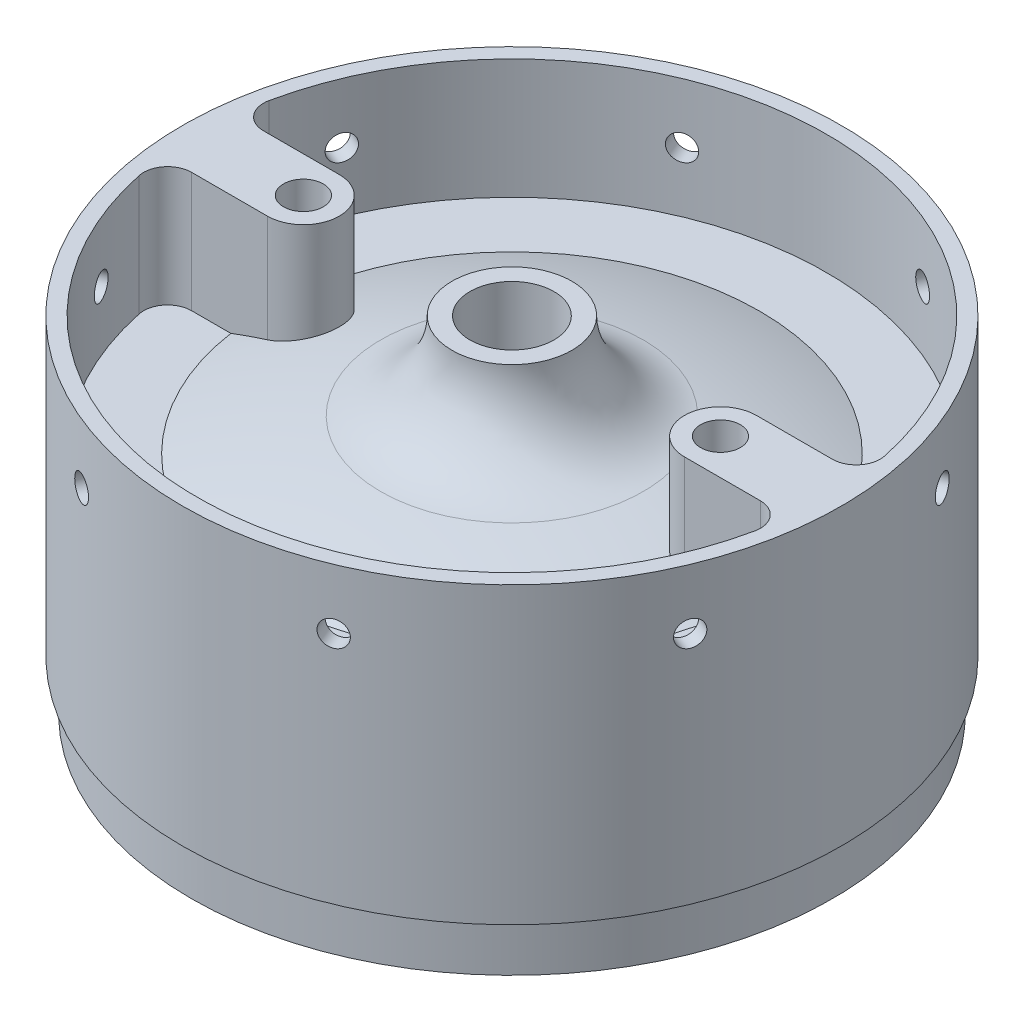
SolidWorks part; units mm, degrees
material "6061-T6 (SS)"
ref_plane "Front Plane" through (0, 0, 0) normal (0, 0, 1) x (1, 0, 0)
ref_plane "Top Plane" through (0, 0, 0) normal (0, 1, 0) x (1, 0, 0)
ref_plane "Right Plane" through (0, 0, 0) normal (1, 0, 0) x (0, 0, -1)
ref_axis "Axis1" through (0, 127.061, 0) along (0, -1, 0)
sketch "Sketch1" plane through (0, 0, 0) normal (0, 0, 1) x (1, 0, 0)
  line L0 (-69.85, 10.6249) -> (-69.85, 73.025)
  line L1 (-67.945, 9.525) -> (-69.85, 10.6249)
  line L2 (0, 127.061) -> (0, -81.9141) construction
  line L3 (-8.9065, 73.025) -> (-12.7, 73.025)
  line L4 (-67.945, 9.525) -> (-67.945, 0)
  line L5 (-67.945, 0) -> (-66.675, 0)
  line L6 (55, 0) -> (-55, 0) construction
  line L7 (-66.675, 73.025) -> (-69.85, 73.025)
  line L8 (-69.85, 10.6249) -> (-67.945, 9.525)
  line L9 (-66.675, 47.625) -> (-52.5032, 47.625)
  line L10 (-8.9065, 73.025) -> (-8.9065, 57.785)
  line L11 (-66.675, 47.625) -> (-66.675, 73.025)
  line L15 (-66.675, 0) -> (-66.675, 9.525)
  line L16 (-66.675, 9.525) -> (-64.3936, 22.4633)
  arc A0 (-64.3936, 22.4633) -> (-52.5032, 40.1167) centre (-45.3436, 22.4633) cw
  arc A1 (-52.5032, 40.1167) -> (-17.4242, 49.2673) centre (0, -89.3418) cw
  arc A2 (-27.8409, 54.6768) -> (-12.7, 73.025) centre (-31.3878, 73.025) ccw
  arc A3 (-52.5032, 47.625) -> (-27.8409, 54.6768) centre (0, -89.3418) cw
  arc A4 (-8.9065, 57.785) -> (-17.4242, 49.2673) centre (-17.4242, 57.785) cw
  point P14 (-67.31, 0)
  dimension "D5" = 19.05
  dimension "D6" = 139.7
  dimension "D7" = 146.685
  dimension "D8" = 63.5
  dimension "D14" = 15.24
  dimension "D2" = 170
  dimension "D3" = 9.525
  dimension "D4" = 1.27
  dimension "D9" = 25.4
  dimension "D10" = 3.175
  dimension "D11" = 12.7
  dimension "D13" = 8.9065
  dimension "D15" = 3.175
  dimension "D16" = 69.85
  dimension "D17" = 120
revolve "Revolve2" add sketch "Sketch1" angle 360 about axis through (0, 127.061, 0) along (0, -1, 0) region at (-46.1743, 45.7628, 0)
sketch "Sketch2" plane through (0, 0, 0) normal (0, 0, 1) x (1, 0, 0)
  line L0 (0, 127.061) -> (0, -81.9141) construction
  line L1 (0, 87.1374) -> (-97.8719, 87.1374)
  line L2 (0, 87.1374) -> (0, -26.2798)
  line L3 (0, -26.2798) -> (-97.8719, -26.2798)
  line L4 (-97.8719, 87.1374) -> (-97.8719, -26.2798)
revolve "Cut-Revolve1" [suppressed] cut sketch "Sketch2" angle 315 about axis through (0, 127.061, 0) along (0, -1, 0)
ref_plane "Plane1" through (0, 60.325, 0) normal (0, 1, 0) x (1, 0, 0)
ref_plane "Plane2" through (0, 0, 0) normal (0.9239, 0, 0.3827) x (0, -1, 0)
ref_axis "Axis2" through (83.9699, 60.325, -202.7212) along (-0.3827, 0, 0.9239)
hole_wizard "#3 (0.213) Diameter Hole1" positions "3DSketch3" profile "Sketch5" hole size "#3" standard "ANSI Inch"
sketch3d "3DSketch3"
  line L0 (83.9699, 60.325, -202.7212) -> (-38.5912, 60.325, 93.1674) construction
  point P0 (-26.7304, 60.325, 64.533)
sketch "Sketch5" plane through (-26.7304, 60.325, 64.533) normal (0, 1, 0) x (0.9239, 0, 0.3827)
  line L0 (0, 0) -> (0, 13.3094)
  line L1 (0, 13.3094) -> (2.7051, 11.684)
  line L2 (2.7051, 11.684) -> (2.7051, 0)
  line L5 (2.7051, 0) -> (0, 0)
  line L10 (0, 13.3094) -> (-2.7051, 11.684) construction
  line L11 (0, -6.35) -> (0, 107.95) construction
  dimension "Hole Dia." = 5.4102
  dimension "Hole Depth" = 11.684
  dimension "Drill Angle" = 118
pattern_circular "CirPattern1" count 8 over 360 about axis through (0, 127.061, 0) along (0, -1, 0) of "#3 (0.213) Diameter Hole1"
cosmetic thread "Cosmetic Thread1" parameters "D2"=6.35
hole_wizard "Q (0.332) Diameter Hole2" positions "Sketch9" profile "Sketch10" hole size "Q" standard "ANSI Inch" end condition through all
sketch "Sketch9" plane through (0, 47.625, 0) normal (0, 1, 0) x (1, 0, 0)
  line L0 (-55, 0) -> (55, 0) construction
  circle A1 centre (0, 0) radius 52.5032 construction
  point P0 (-44.196, 0)
  dimension "D1" = 44.196
sketch "Sketch10" plane through (-44.196, 47.625, 0) normal (1, 0, 0) x (0, 0, 1)
  line L0 (0, 0) -> (0, 47.625)
  line L1 (0, 47.625) -> (4.2164, 47.625)
  line L2 (4.2164, 47.625) -> (4.2164, 0)
  line L5 (4.2164, 0) -> (0, 0)
  line L11 (0, -6.35) -> (0, 107.95) construction
  dimension "Thru Hole Dia." = 8.4328
  dimension "Thru Hole Depth" = 47.625
sketch "Sketch11" plane through (0, 47.625, 0) normal (0, 1, 0) x (1, 0, 0)
  line L0 (-66.2381, 7.62) -> (-44.196, 7.62)
  line L1 (-66.2382, -7.6198) -> (-44.1961, -7.62)
  circle A0 centre (0, 0) radius 66.675 construction
  arc A2 (-44.196, 7.62) -> (-44.1961, -7.62) centre (-44.196, 0) cw
  circle A3 centre (-44.196, 0) radius 4.2164 construction
  circle A5 centre (0, 0) radius 66.675
  arc A6 (-66.2381, 7.62) -> (-66.2382, -7.6198) centre (0, 0) ccw
  dimension "D1" = 7.62
  dimension "D2" = 7.62
  dimension "D3" = 180
  dimension "D4" = 0
extrude "Boss-Extrude1" add sketch "Sketch11" along normal up to surface (25.4 mm away) up to face at (0, 73.025, 69.85)
fillet "Fillet1" radius 5.08 2 edges at (-66.2381, 60.325, -7.62) (-66.2382, 60.325, 7.6198)
hole_wizard "Q (0.332) Diameter Hole3" positions "Sketch12" profile "Sketch13" hole size "Q" standard "ANSI Inch" end condition up to next
sketch "Sketch12" plane through (0, 47.625, 0) normal (0, -1, 0) x (-1, 0, 0)
  circle A0 centre (44.196, 0) radius 4.2164 construction
  point P0 (44.196, 0)
  point P4 (0, 0)
sketch "Sketch13" plane through (-44.196, 47.625, 0) normal (1, 0, 0) x (0, 0, -1)
  line L0 (0, 0) -> (0, 25.401)
  line L1 (0, 25.401) -> (4.2164, 25.401)
  line L2 (4.2164, 25.401) -> (4.2164, 0)
  line L5 (4.2164, 0) -> (0, 0)
  line L11 (0, -6.35) -> (0, 107.95) construction
  dimension "Thru Hole Dia." = 8.4328
  dimension "Thru Hole Depth" = 25.401
mirror "Mirror1" about plane through (0, 0, 0) normal (1, 0, 0) of "Boss-Extrude1", "Fillet1", "Q (0.332) Diameter Hole3"
